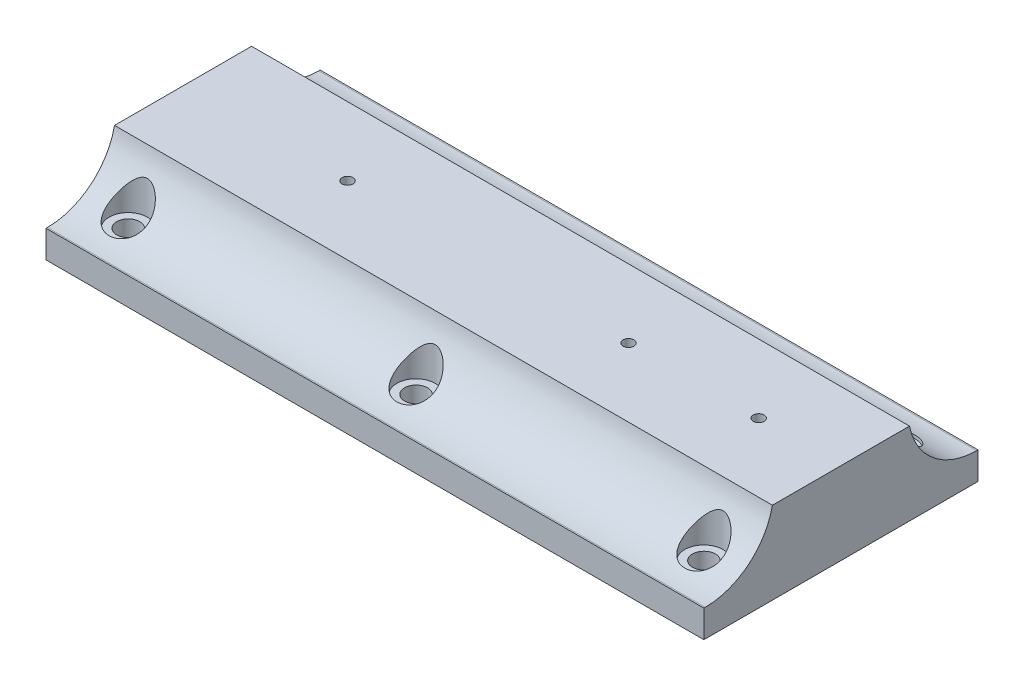
SolidWorks part; units mm, degrees
ref_plane "Front Plane" through (0, 0, 0) normal (0, 0, 1) x (1, 0, 0)
ref_plane "Top Plane" through (0, 0, 0) normal (0, 1, 0) x (1, 0, 0)
ref_plane "Right Plane" through (0, 0, 0) normal (1, 0, 0) x (0, 0, -1)
sketch "Sketch2" plane through (0, 0, 0) normal (0, 1, 0) x (1, 0, 0)
  line L0 (-46.8981, 34.5466) -> (-46.8981, -15.4534)
  line L1 (-46.8981, -15.4534) -> (73.1019, -15.4534)
  line L2 (73.1019, -15.4534) -> (73.1019, 34.5466)
  line L3 (73.1019, 34.5466) -> (-46.8981, 34.5466)
  dimension "D1" = 120
  dimension "D2" = 50
extrude "Boss-Extrude1" add sketch "Sketch2" along normal blind 15
sketch "Sketch3" plane through (0, 0, 0) normal (0, 1, 0) x (1, 0, 0)
  line L0 (74.3548, 9.5466) -> (-56.2815, 9.5466) construction
  line L1 (63.1019, 9.5466) -> (63.1019, 17.0466)
  line L2 (63.1019, 17.0466) -> (3.1019, 17.0466)
  line L3 (3.1019, 17.0466) -> (3.1019, 19.5466)
  line L4 (3.1019, 19.5466) -> (-36.8981, 19.5466)
  line L5 (-36.8981, 19.5466) -> (-36.8981, 9.5466)
  line L6 (-36.8981, 9.5466) -> (63.1019, 9.5466)
  line L7 (73.1019, -15.4534) -> (73.1019, 34.5466) construction
  line L9 (-46.8981, -15.4534) -> (73.1019, -15.4534) construction
  dimension "D1" = 60
  dimension "D2" = 40
  dimension "D3" = 10
  dimension "D4" = 25
  dimension "D5" = 10
  dimension "D6" = 7.5
revolve "Cut-Revolve8" cut sketch "Sketch3" angle 360 about L0
ref_plane "Ebene1" through (63.1019, 0, 0) normal (-1, 0, 0) x (0, 0, 1)
sketch "Skizze2" plane through (63.1019, 0, 0) normal (-1, 0, 0) x (0, 0, 1)
  line L0 (-22.101, 0) -> (5.7524, 0) construction
  line L1 (-2.0466, 0) -> (-17.0466, 0) construction
  line L2 (-9.5466, -15.2765) -> (-9.5466, 13.7911) construction
  line L3 (-3.5466, 0) -> (-2.0466, 0)
  line L4 (-2.0466, 0) -> (-17.0466, 0) construction
  line L5 (-34.5466, 15) -> (-34.5466, 0) construction
  line L6 (15.4534, 15) -> (15.4534, 0) construction
  line L7 (-4.9281, 3.83) -> (-3.7734, 4.7875)
  arc A0 (-2.0466, 0) -> (-3.7734, 4.7875) centre (-9.5466, 0) ccw
  arc A1 (-3.5466, 0) -> (-4.9281, 3.83) centre (-9.5466, 0) ccw
  dimension "D1" = 1.5
  dimension "D2" = 7.5
  dimension "D3" = 1.5
  dimension "D4" = 3.83
ref_plane "Ebene2" through (28.1019, 0, 0) normal (-1, 0, 0) x (0, 0, 1)
extrude "Aufsatz-Linear austragen3" add sketch "Skizze2" along normal blind 47.5
ref_plane "Ebene3" through (0, 0, -9.5466) normal (0, 0, 1) x (1, 0, 0)
mirror "Spiegeln1" about plane through (0, 0, -9.5466) normal (0, 0, 1) of "Aufsatz-Linear austragen3"
sketch "Skizze7" plane through (63.1019, 0, 0) normal (-1, 0, 0) x (0, 0, 1)
  line L0 (-3.5466, 0) -> (-15.5466, 0) construction
  circle A0 centre (-9.5466, 0) radius 7.5
  arc A1 (-3.7734, 4.7875) -> (-15.3198, 4.7875) centre (-9.5466, 0) ccw construction
extrude "Schnitt-Linear austragen2" cut sketch "Skizze7" against normal blind 12.5 from surface starting at plane "Ebene2"
extrude "Schnitt-Linear austragen3" cut sketch "Skizze7<2>" along normal blind 10 contours A0
sketch "Skizze7<2>" plane through (63.1019, 0, 0) normal (-1, 0, 0) x (0, 0, 1) same geometry as "Skizze7"
sketch "Skizze8" plane through (0, 15, 0) normal (0, 1, 0) x (1, 0, 0)
  line L0 (91.3144, 9.5466) -> (-68.5218, 9.5466) construction
  line L1 (73.1019, 34.5466) -> (-46.8981, 34.5466) construction
  line L2 (-46.8981, -15.4534) -> (73.1019, -15.4534) construction
  line L3 (73.1019, -15.4534) -> (73.1019, 34.5466) construction
  line L4 (-46.8981, 34.5466) -> (-46.8981, -15.4534) construction
  circle A0 centre (58.1019, 9.5466) radius 1
  circle A1 centre (34.3519, 9.5466) radius 1
  circle A2 centre (-16.8981, 9.5466) radius 1
  dimension "D1" = 2
  dimension "D2" = 23.75
  dimension "D3" = 15
  dimension "D4" = 30
extrude "Schnitt-Linear austragen4" cut sketch "Skizze8" against normal up to next
sketch "Skizze9" plane through (-46.8981, 0, 0) normal (-1, 0, 0) x (0, 0, 1)
  line L0 (-34.5466, 5) -> (-22.0466, 5)
  line L1 (2.9534, 5) -> (2.9534, 15)
  line L2 (15.4534, 0) -> (-34.5466, 0) construction
  line L4 (2.9534, 5) -> (15.4534, 5)
  line L5 (15.4534, 15) -> (15.4534, 0) construction
  line L6 (-34.5466, 5) -> (-34.5466, 15)
  line L7 (-34.5466, 15) -> (15.4534, 15)
  line L8 (15.4534, 15) -> (15.4534, 5)
  line L9 (2.9534, 15) -> (-22.0466, 15)
  line L10 (-22.0466, 15) -> (-22.0466, 5)
  line M8 (15.4534, 0) -> (15.4534, 15)
  line M9 (15.4534, 15) -> (-34.5466, 15)
  line M10 (-34.5466, 15) -> (-34.5466, 0)
  dimension "D1" = 5
  dimension "D2" = 12.5
  dimension "D3" = 12.5
extrude "Schnitt-Linear austragen5" cut sketch "Skizze9" against normal through all contours L10 L7 L0 M10 | L4 M9 M8 region at (-46.8981, 10, -28.2966) region at (-46.8981, 10, 9.2034)
sketch "Skizze10" plane through (0, 5, 0) normal (0, 1, 0) x (1, 0, 0)
  line L0 (73.1019, 34.5466) -> (73.1019, 22.0466) construction
  line L1 (73.1019, 34.5466) -> (-46.8981, 34.5466) construction
  circle A0 centre (65.6019, 27.0466) radius 2.1
  dimension "D1" = 4.2
  dimension "D2" = 7.5
  dimension "D3" = 7.5
extrude "Schnitt-Linear austragen7" cut sketch "Skizze10" against normal through all
sketch "Skizze11" plane through (0, 5, 0) normal (0, 1, 0) x (1, 0, 0)
  line L0 (80.5883, 9.5466) -> (-93.0916, 9.5466) construction
  line L1 (73.1019, 34.5466) -> (-46.8981, 34.5466) construction
  line L2 (73.1019, -15.4534) -> (-46.8981, -15.4534) construction
mirror "Spiegeln2" about plane through (0, 0, -9.5466) normal (0, 0, 1) of "Schnitt-Linear austragen7"
ref_plane "Ebene4" through (13.1019, 0, 0) normal (1, 0, 0) x (0, 0, -1)
mirror "Spiegeln3" about plane through (13.1019, 0, 0) normal (1, 0, 0) of "Schnitt-Linear austragen7", "Spiegeln2"
sketch "Skizze12" plane through (0, 5, 0) normal (0, 1, 0) x (1, 0, 0)
  line L0 (73.1019, -15.4534) -> (73.1019, 34.5466) construction
  line L1 (73.1019, 34.5466) -> (-46.8981, 34.5466) construction
  line L2 (73.1019, -15.4534) -> (-46.8981, -15.4534) construction
  circle A0 centre (13.1019, 27.0466) radius 2.1
  circle A1 centre (13.1019, -7.9534) radius 2.1
  circle A2 centre (65.6019, -7.9534) radius 2.1 construction
  dimension "D1" = 60
  dimension "D2" = 7.5
  dimension "D3" = 7.5
extrude "Schnitt-Linear austragen8" cut sketch "Skizze12" against normal blind 10
fillet "Fillet2" radius 12.5 1 edges at (13.1019, 5, 2.9534)
fillet "Fillet3" radius 12.5 1 edges at (13.1019, 5, -22.0466)
ref_plane "Plane1" through (0, 25, 0) normal (0, 1, 0) x (1, 0, 0)
sketch "Sketch7" plane through (0, 25, 0) normal (0, 1, 0) x (1, 0, 0)
  circle A0 centre (-39.3981, -7.9534) radius 3.5
  circle A1 centre (13.1019, -7.9534) radius 3.5
  circle A2 centre (65.6019, -7.9534) radius 3.5
  circle A3 centre (13.1019, 27.0466) radius 3.5
  circle A4 centre (-39.3981, 27.0466) radius 3.5
  circle A5 centre (65.6019, 27.0466) radius 3.5
  dimension "D1" = 7
  dimension "D2" = 7
  dimension "D3" = 7
  dimension "D4" = 7
  dimension "D5" = 7
  dimension "D6" = 7
extrude "Cut-Extrude2" cut sketch "Sketch7" against normal blind 20
